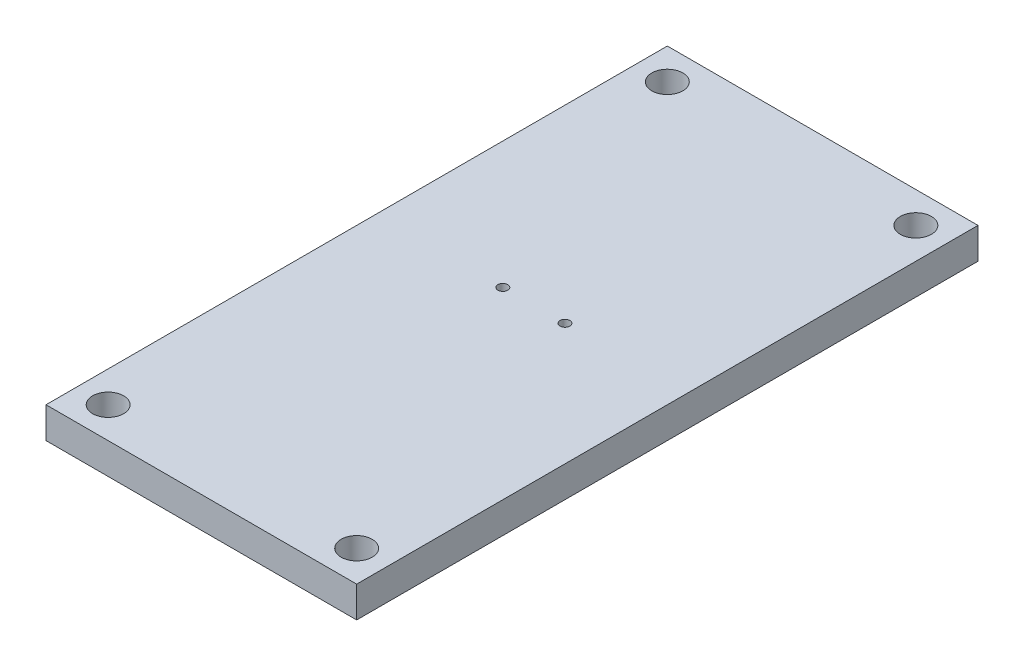
SolidWorks part; units mm, degrees
ref_plane "Front Plane" through (0, 0, 0) normal (0, 0, 1) x (1, 0, 0)
ref_plane "Top Plane" through (0, 0, 0) normal (0, 1, 0) x (1, 0, 0)
ref_plane "Right Plane" through (0, 0, 0) normal (1, 0, 0) x (0, 0, -1)
sketch "Sketch1" plane through (0, 0, 0) normal (0, 1, 0) x (1, 0, 0)
  line L1 (25, -50) -> (-25, -50)
  line L2 (25, -50) -> (25, 50)
  line L3 (25, 50) -> (-25, 50)
  line L4 (-25, -50) -> (-25, 50)
  line L5 (25, -50) -> (-25, 50) construction
  line L6 (25, 50) -> (-25, -50) construction
  point P0 (0, 0)
  dimension "D1" = 100
  dimension "D2" = 50
extrude "Boss-Extrude1" add sketch "Sketch1" along normal blind 5
sketch "Sketch2" plane through (0, 5, 0) normal (0, 1, 0) x (1, 0, 0)
  line L1 (-10, 0) -> (10, 0)
  line L3 (-10, 11) -> (10, 11)
  line L7 (11, 0) -> (11, 11)
  line L9 (-10, 11) -> (-11, 11)
  line L10 (-11, 11) -> (11, 11)
  line L11 (10, 0) -> (11, 0)
  line L12 (11, 0) -> (-11, 0)
  line L13 (-10, 0) -> (-10, 11) construction
  line L14 (10, 0) -> (10, 11) construction
  line L15 (11, -1) -> (11, 12) construction
  line L16 (-11, 12) -> (11, 12) construction
  line L17 (-11, -1) -> (-11, 12) construction
  line L18 (-11, -1) -> (11, -1) construction
  line L19 (-11, 11) -> (-11, 0) construction
  line L21 (0, 3.4802) -> (0, 7.7866) construction
  circle A2 centre (5.4089, 3.116) radius 0.7913
  circle A3 centre (-4.5911, 3.116) radius 0.7913
  dimension "D1" = 11
extrude "Cut-Extrude1" cut sketch "Sketch2" against normal blind 6 and the other way through all contours L12 L1 L11 L7 L10 L3 L9 | A3
extrude "Cut-Extrude2" cut sketch "Sketch2<3>" against normal through all both and the other way through all contours A3 | A2 region at (-4.5911, 5, -3.116)
sketch "Sketch2<3>" plane through (0, 5, 0) normal (0, 1, 0) x (1, 0, 0) same geometry as "Sketch2"
sketch "Sketch3" plane through (0, 0, 0) normal (0, -1, 0) x (1, 0, 0)
  line L0 (0, 0) -> (0, 4.0511) construction
  line L1 (0, 4.0511) -> (0, 0) construction
  line L2 (0, 0) -> (6.1277, 0) construction
  line L3 (-25, -50) -> (-25, 50) construction
  line L4 (-25, 50) -> (25, 50) construction
  circle A0 centre (-20, 45) radius 2.5
  circle A1 centre (20, 45) radius 2.5
  circle A2 centre (20, -45) radius 2.5
  circle A3 centre (-20, -45) radius 2.5
  dimension "D1" = 5
  dimension "D2" = 5
extrude "Cut-Extrude3" cut sketch "Sketch3" against normal through all both and the other way through all
